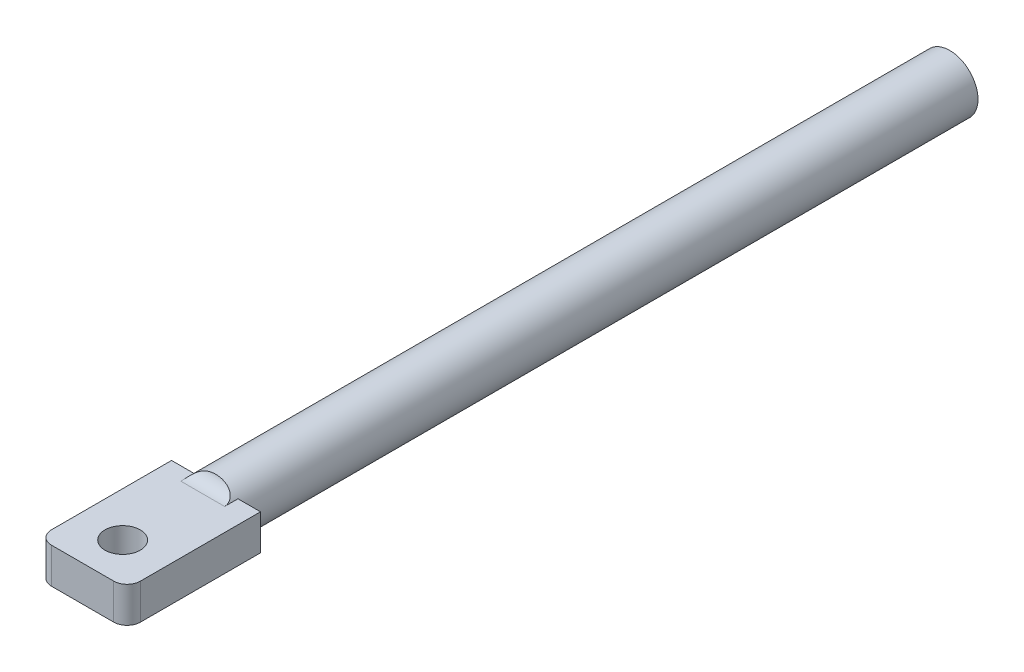
SolidWorks part; units mm, degrees
ref_plane "Alzado" through (0, 0, 0) normal (0, 0, 1) x (1, 0, 0)
ref_plane "Planta" through (0, 0, 0) normal (0, 1, 0) x (1, 0, 0)
ref_plane "Vista lateral" through (0, 0, 0) normal (1, 0, 0) x (0, 0, -1)
sketch "Croquis1" plane through (0, 0, 0) normal (0, 0, 1) x (1, 0, 0)
  circle A0 centre (0, 0) radius 6.35
  dimension "D1" = 12.7
extrude "Saliente-Extruir1" add sketch "Croquis1" along normal blind 165
sketch "Croquis2" plane through (0, 0, 165) normal (0, 0, 1) x (1, 0, 0)
  line L0 (0, 6.35) -> (0, -6.35) construction
  line L2 (-10, -4) -> (10, -4)
  line L3 (-10, -4) -> (-10, 4)
  line L4 (-10, 4) -> (10, 4)
  line L5 (10, -4) -> (10, 4)
  line L6 (-10, -4) -> (10, 4) construction
  line L7 (-10, 4) -> (10, -4) construction
  circle A0 centre (0, 0) radius 6.35 construction
  point P5 (0, 0)
  dimension "D1" = 20
  dimension "D2" = 8
extrude "Saliente-Extruir2" add sketch "Croquis2" along normal blind 30
fillet "Redondeo1" radius 3 1 edges at (0, 4, 165)
fillet "Redondeo2" radius 3 1 edges at (0, -4, 165)
sketch "Croquis3" plane through (0, -4, 0) normal (0, -1, 0) x (1, 0, 0)
  line L0 (0, 195) -> (0, 186) construction
  line L1 (-10, 195) -> (10, 195) construction
  circle A0 centre (0, 186) radius 3.9687
  dimension "D2" = 7.9375
  dimension "D1" = 9
extrude "Cortar-Extruir1" cut sketch "Croquis3" against normal blind 30
fillet "Redondeo3" radius 3 2 edges at (10, 0, 195) (-10, 0, 195)
